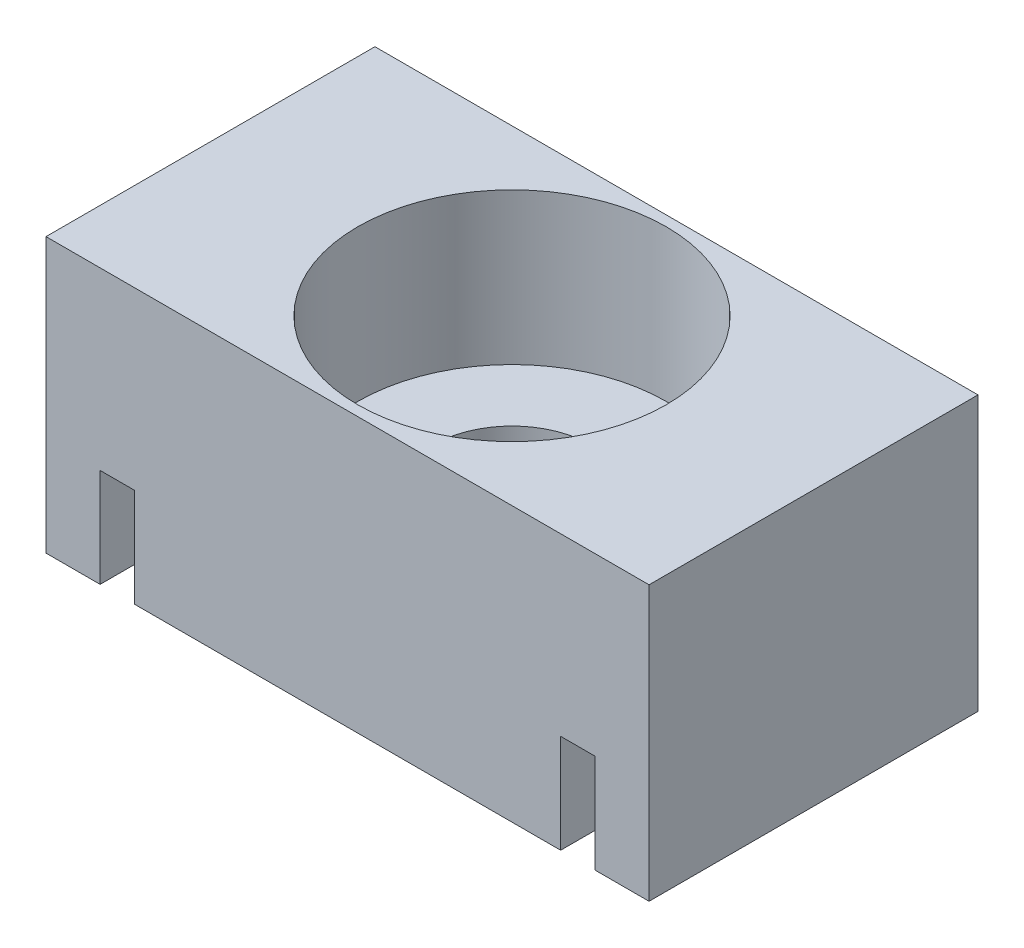
SolidWorks part; units mm, degrees
material "Nylon 6/10"
ref_plane "Front Plane" through (0, 0, 0) normal (0, 0, 1) x (1, 0, 0)
ref_plane "Top Plane" through (0, 0, 0) normal (0, 1, 0) x (1, 0, 0)
ref_plane "Right Plane" through (0, 0, 0) normal (1, 0, 0) x (0, 0, -1)
sketch "Sketch1" plane through (0, 0, 0) normal (0, 1, 0) x (1, 0, 0)
  line L1 (-6.985, -3.81) -> (6.985, -3.81)
  line L2 (-6.985, -3.81) -> (-6.985, 3.81)
  line L3 (-6.985, 3.81) -> (6.985, 3.81)
  line L4 (6.985, -3.81) -> (6.985, 3.81)
  line L5 (-6.985, -3.81) -> (6.985, 3.81) construction
  line L6 (-6.985, 3.81) -> (6.985, -3.81) construction
  point P0 (0, 0)
  dimension "D1" = 13.97
  dimension "D2" = 7.62
extrude "Base" add sketch "Sketch1" along normal blind 6.35
sketch "Sketch2" plane through (0, 0, 0) normal (0, -1, 0) x (1, 0, 0)
  line L0 (-5.334, 3.81) -> (-5.334, 2.3368) construction
  line L1 (-6.985, 3.81) -> (6.985, 3.81) construction
  line L2 (-4.9371, 3.81) -> (-4.9371, 2.3368)
  line L3 (-5.7309, 3.81) -> (-5.7309, 2.3368)
  line L4 (5.334, 3.81) -> (5.334, 2.3368) construction
  line L5 (5.7309, 3.81) -> (5.7309, 2.3368)
  line L6 (4.9371, 3.81) -> (4.9371, 2.3368)
  line L7 (0, 0) -> (0, 225.9023) construction
  arc A0 (-4.9371, 3.81) -> (-5.7309, 3.81) centre (-5.334, 3.81) ccw
  arc A1 (-5.7309, 2.3368) -> (-4.9371, 2.3368) centre (-5.334, 2.3368) ccw
  arc A2 (5.7309, 3.81) -> (4.9371, 3.81) centre (5.334, 3.81) ccw
  arc A3 (4.9371, 2.3368) -> (5.7309, 2.3368) centre (5.334, 2.3368) ccw
  point P4 (-5.334, 3.0734)
  point P9 (5.334, 3.0734)
  dimension "D1" = 0.7937
  dimension "D2" = 10.668
  dimension "D3" = 1.4732
extrude "BoxSlots" cut sketch "Sketch2" against normal blind 2.286
hole_wizard "MoutingHole" positions "Sketch6" profile "Sketch5" counterbore size "#6" standard "ANSI Inch" end condition through all
sketch "Sketch6" plane through (0, 6.35, 0) normal (0, 1, 0) x (1, 0, 0)
  point P0 (0, 0)
sketch "Sketch5" plane through (0, 6.35, 0) normal (1, 0, 0) x (0, 0, 1)
  line L0 (0, 0) -> (0, 6.35)
  line L1 (0, 6.35) -> (1.8288, 6.35)
  line L3 (1.8288, 6.35) -> (1.8288, 3.5052)
  line L4 (1.8288, 3.5052) -> (3.5725, 3.5052)
  line L5 (3.5725, 3.5052) -> (3.5725, 0)
  line L7 (3.5725, 0) -> (0, 0)
  line L11 (0, -6.35) -> (0, 107.95) construction
  dimension "Thru Hole Dia." = 3.6576
  dimension "Thru Hole Depth" = 6.35
  dimension "C'Bore Dia." = 7.145
  dimension "C'Bore Depth" = 3.5052
